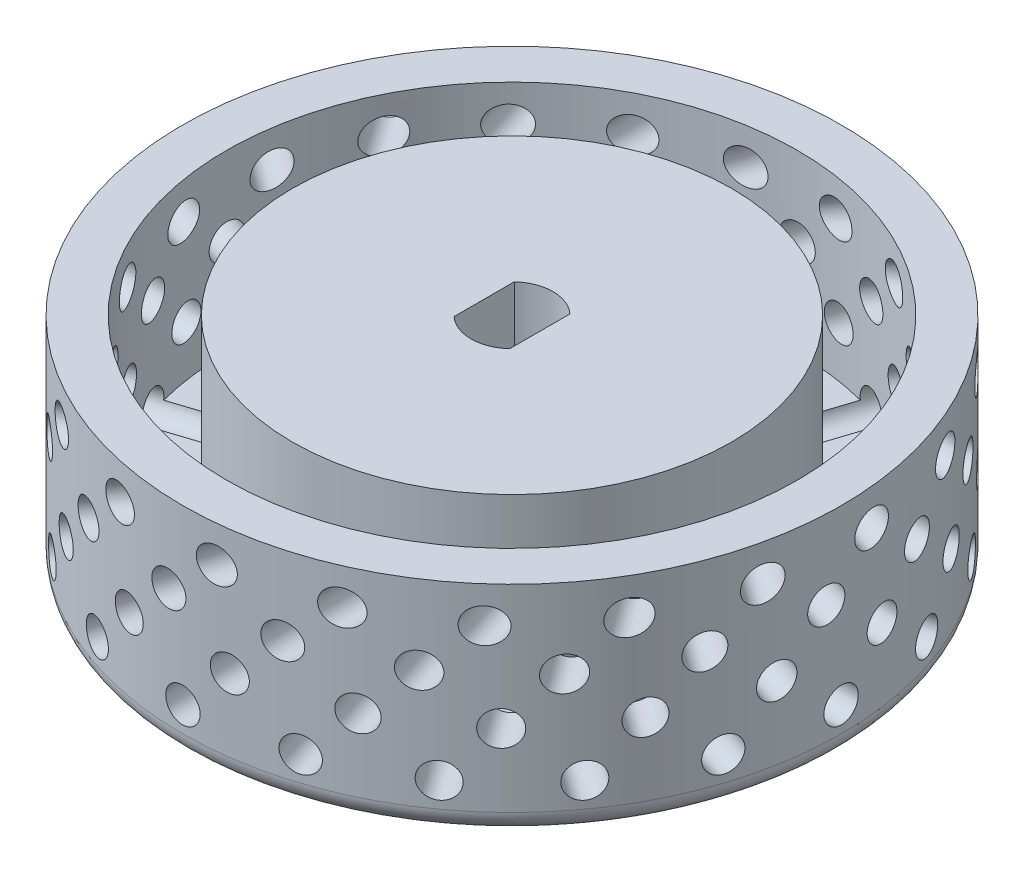
SolidWorks part; units mm, degrees
ref_plane "Alzado" through (0, 0, 0) normal (0, 0, 1) x (1, 0, 0)
ref_plane "Planta" through (0, 0, 0) normal (0, 1, 0) x (1, 0, 0)
ref_plane "Vista lateral" through (0, 0, 0) normal (1, 0, 0) x (0, 0, -1)
sketch "Croquis1" plane through (0, 0, 0) normal (0, 1, 0) x (1, 0, 0)
  circle A0 centre (0, 0) radius 22.5
  dimension "D1" = 45
extrude "Saliente-Extruir1" add sketch "Croquis1" along normal blind 15
shell "Vaciado1" thickness 3 removed face at (0, 15, 22.5)
fillet "Redondeo1" radius 1.5 1 edges at (0, 0, 22.5)
sketch "Croquis2" plane through (0, 0, 0) normal (0, -1, 0) x (1, 0, 0)
  circle A0 centre (0, 0) radius 8.1
  dimension "D1" = 16.2
extrude "Saliente-Extruir2" add sketch "Croquis2" along normal blind 4
fillet "Redondeo2" radius 1.5 1 edges at (0, -4, -8.1)
sketch "Croquis3" plane through (0, -4, 0) normal (0, -1, 0) x (1, 0, 0)
  circle A0 centre (0, 0) radius 1.55
  dimension "D1" = 3.1
sketch "Croquis5" plane through (0, 3, 0) normal (0, 1, 0) x (1, 0, 0)
  circle A0 centre (0, 0) radius 15
  dimension "D1" = 30
extrude "Saliente-Extruir3" add sketch "Croquis5" along normal up to surface (12 mm away) up to face at (0, 15, 19.5)
sketch "Croquis6" plane through (0, 15, 0) normal (0, 1, 0) x (1, 0, 0)
  line L2 (-1.9, 2.0567) -> (-1.9, -2.0567)
  line L4 (1.9, 2.0567) -> (1.9, -2.0567)
  circle A0 centre (0, 0) radius 2.8
  dimension "D1" = 5.6
extrude "Cortar-Extruir3" cut sketch "Croquis6" against normal blind 7 contours L4 A0 L2 region at (0, 15, 0)
hole_wizard "Refrentado para tornillo con cabeza troncocónica de M2.51" positions "Croquis3D3" profile "Croquis10" counterbore size "M2.5" standard "Ansi Metric" end condition through all
sketch3d "Croquis3D3"
  point P0 (0, 0, 0)
  point P4 (0, -4, 0)
sketch "Croquis10" plane through (0, -4, 0) normal (1, 0, 0) x (0, 0, -1)
  line L0 (0, 0) -> (0, 19)
  line L1 (0, 19) -> (1.45, 19)
  line L3 (1.45, 19) -> (1.45, 2.1)
  line L4 (1.45, 2.1) -> (3, 2.1)
  line L5 (3, 2.1) -> (3, 0)
  line L7 (3, 0) -> (0, 0)
  line L11 (0, -6.35) -> (0, 107.95) construction
  dimension "Diámetro de taladro hasta el siguiente" = 2.9
  dimension "Profundidad de taladro hasta el siguiente" = 19
  dimension "Diámetro de refrentado" = 6
  dimension "Profundidad de refrentado" = 2.1
sketch "Croquis4" plane through (0, -4, 0) normal (0, -1, 0) x (1, 0, 0)
  circle A0 centre (0, 0) radius 8.1
  spline S0 degree 2 poles (-2.6489, 7.6546) (-0.1271, 0.0255) (3.0481, 7.5046) knots 0 0 0 1 1 1
  spline S1 degree 2 poles (6.4614, 4.8847) (-0.015, 0.1288) (8.0792, -0.5799) knots 0 0 0 1 1 1
  spline S2 degree 2 poles (6.6423, -4.6357) (0.1178, 0.0541) (1.9451, -7.863) knots 0 0 0 1 1 1
  spline S3 degree 2 poles (-2.3562, -7.7497) (0.0879, -0.0953) (-6.8771, -4.2797) knots 0 0 0 1 1 1
  spline S4 degree 2 poles (-8.0985, -0.1539) (-0.0635, -0.113) (-6.1954, 5.218) knots 0 0 0 1 1 1
sketch "Croquis11" plane through (0, -1.9, 0) normal (0, -1, 0) x (-1, 0, 0)
  circle A0 centre (0, 0) radius 2.59
  dimension "D1" = 5.18
sketch "Croquis12" plane through (0, -1.9, 0) normal (0, -1, 0) x (1, 0, 0)
  circle A0 centre (0, 0) radius 2.9756
extrude "Cortar-Extruir4" cut sketch "Croquis12" against normal blind 5
ref_plane "Plano1" through (0, 0, -22.5) normal (0, 0, -1) x (-1, 0, 0)
sketch "Croquis13" plane through (0, 0, -22.5) normal (0, 0, -1) x (-1, 0, 0)
  line L0 (0, -4) -> (0, -14.8158)
  line L1 (-1.55, -4) -> (1.55, -4) construction
  circle A0 centre (0, 3.2101) radius 1.175
  circle A1 centre (3, 6.4694) radius 1.175
  circle A2 centre (6, 9.5957) radius 1.175
  circle A3 centre (9, 12.5224) radius 1.175
  dimension "D1" = 2.35
  dimension "D2" = 2.35
  dimension "D6" = 2.35
  dimension "D7" = 2.35
  dimension "D3" = 3
  dimension "D4" = 3
  dimension "D5" = 3
extrude "Cortar-Extruir5" cut sketch "Croquis13" against normal blind 7 contours A2 | A1 | A0 | A3 region at (0, 3.2101, -22.5) region at (-3, 6.4694, -22.5) region at (-6, 9.5957, -22.5)
pattern_circular "MatrizC1" count 20 over 360 about axis through (0, 15, 0) along (0, 1, 0) of "Cortar-Extruir5"
sketch "Croquis17" plane through (0, 15, 0) normal (0, 1, 0) x (1, 0, 0)
  line L0 (14.9923, -0.4814) -> (22.4948, -0.4814)
  line L1 (22.4948, -0.4814) -> (27.6948, -0.4814)
  circle A0 centre (0, 0) radius 22.5 construction
  dimension "D1" = 5.2
